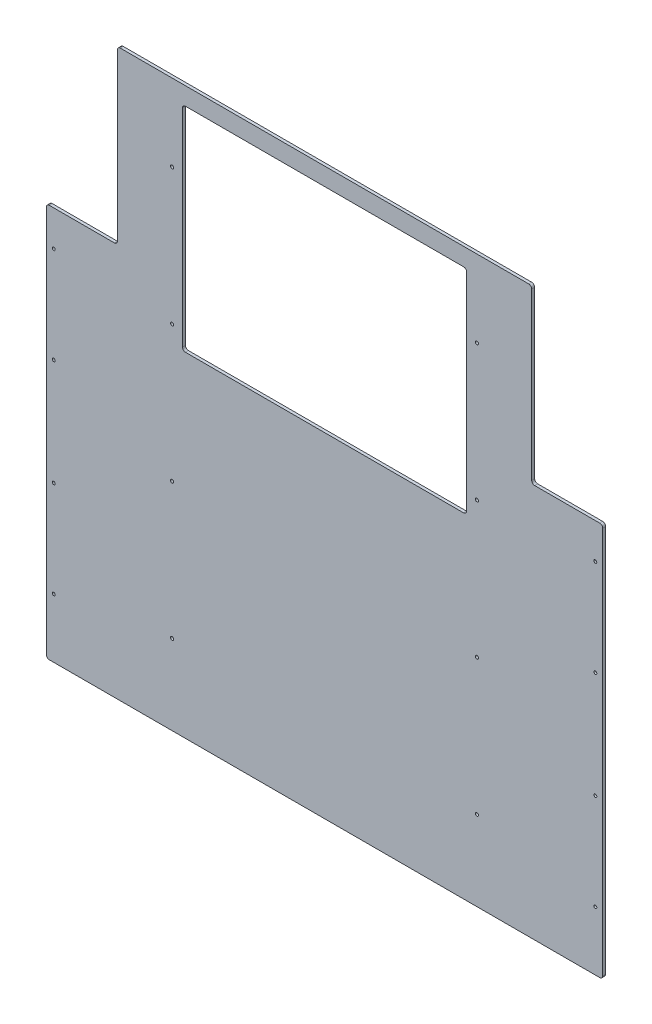
SolidWorks part; units mm, degrees
material "PC High Viscosity"
ref_plane "Front Plane" through (0, 0, 0) normal (0, 0, 1) x (1, 0, 0)
ref_plane "Top Plane" through (0, 0, 0) normal (0, 1, 0) x (1, 0, 0)
ref_plane "Right Plane" through (0, 0, 0) normal (1, 0, 0) x (0, 0, -1)
sketch "Sketch1" plane through (0, 0, 0) normal (0, 0, 1) x (1, 0, 0)
  line L1 (0, 0) -> (1193.8, 0)
  line L2 (0, 0) -> (0, 1212.85)
  line L3 (0, 1212.85) -> (1193.8, 1212.85)
  line L4 (1193.8, 0) -> (1193.8, 1212.85)
  dimension "D1" = 1212.85
  dimension "D2" = 1193.8
extrude "Boss-Extrude1" add sketch "Sketch1" along normal blind 6.35
sketch "Sketch2" plane through (0, 0, 6.35) normal (0, 0, 1) x (1, 0, 0)
  line L0 (596.9, 1212.85) -> (596.9, 0) construction
  line L1 (1193.8, 1212.85) -> (0, 1212.85) construction
  line L2 (0, 0) -> (1193.8, 0) construction
  line L3 (901.7, 1174.75) -> (292.1, 1174.75)
  line L4 (292.1, 1174.75) -> (292.1, 717.55)
  line L5 (292.1, 717.55) -> (901.7, 717.55)
  line L6 (901.7, 1174.75) -> (901.7, 717.55)
  point P11 (596.9, 717.55)
  point P12 (596.9, 1174.75)
  dimension "D1" = 609.6
  dimension "D2" = 457.2
  dimension "D3" = 38.1
extrude "Cut-Extrude1" cut sketch "Sketch2" against normal through all
sketch "Sketch3" plane through (0, 0, 6.35) normal (0, 0, 1) x (1, 0, 0)
  line L0 (0, 1212.85) -> (0, 0) construction
  line L1 (0, 1174.75) -> (152.4, 1174.75)
  line L2 (0, 1174.75) -> (0, 844.55)
  line L3 (0, 844.55) -> (152.4, 844.55)
  line L4 (152.4, 1174.75) -> (152.4, 844.55)
  line L5 (596.9, 1212.85) -> (596.9, 0) construction
  line L6 (1193.8, 1212.85) -> (0, 1212.85) construction
  line L7 (0, 0) -> (1193.8, 0) construction
  line L8 (1041.4, 1174.75) -> (1041.4, 844.55)
  line L9 (1193.8, 844.55) -> (1041.4, 844.55)
  line L10 (1193.8, 1174.75) -> (1193.8, 844.55)
  line L11 (1193.8, 1174.75) -> (1041.4, 1174.75)
  dimension "D1" = 38.1
  dimension "D2" = 368.3
  dimension "D3" = 152.4
extrude "Cut-Extrude2" cut sketch "Sketch3" against normal through all
hole_wizard "1/4 (0.25) Diameter Hole1" positions "Sketch4" profile "Sketch5" hole size "1/4" standard "ANSI Inch" end condition through all
sketch "Sketch4" plane through (0, 0, 6.35) normal (0, 0, 1) x (1, 0, 0)
  line L0 (596.9, 0) -> (596.9, 717.55) construction
  line L1 (0, 0) -> (1193.8, 0) construction
  line L2 (292.1, 717.55) -> (901.7, 717.55) construction
  line L3 (0, 844.55) -> (0, 0) construction
  point P0 (15.875, 127)
  point P2 (15.875, 333.375)
  point P4 (15.875, 561.975)
  point P6 (15.875, 768.35)
  point P17 (1177.925, 768.35)
  point P18 (1177.925, 561.975)
  point P19 (1177.925, 333.375)
  point P20 (1177.925, 127)
  dimension "D1" = 15.875
  dimension "D2" = 127
  dimension "D3" = 333.375
  dimension "D4" = 561.975
  dimension "D5" = 768.35
sketch "Sketch5" plane through (15.875, 127, 6.35) normal (1, 0, 0) x (0, -1, 0)
  line L0 (0, 0) -> (0, 6.35)
  line L1 (0, 6.35) -> (3.175, 6.35)
  line L2 (3.175, 6.35) -> (3.175, 0)
  line L5 (3.175, 0) -> (0, 0)
  line L11 (0, -6.35) -> (0, 107.95) construction
  dimension "Thru Hole Dia." = 6.35
  dimension "Thru Hole Depth" = 6.35
hole_wizard "1/4 Clearance Hole1" positions "Sketch6" profile "Sketch7" hole size "1/4" standard "ANSI Inch" end condition through all
sketch "Sketch6" plane through (0, 0, 6.35) normal (0, 0, 1) x (1, 0, 0)
  line L1 (292.1, 1212.85) -> (247.65, 1212.85)
  line L2 (292.1, 1212.85) -> (292.1, 0)
  line L3 (292.1, 0) -> (247.65, 0)
  line L4 (247.65, 1212.85) -> (247.65, 0)
  line L5 (1193.8, 1212.85) -> (0, 1212.85) construction
  line L6 (0, 0) -> (1193.8, 0) construction
  line L7 (596.9, 0) -> (596.9, 1212.85) construction
  line L8 (269.875, 1212.85) -> (269.875, 0) construction
  line L9 (923.925, 1212.85) -> (923.925, 0) construction
  line L10 (946.15, 1212.85) -> (946.15, 0)
  line L11 (901.7, 0) -> (946.15, 0)
  line L12 (901.7, 1212.85) -> (901.7, 0)
  line L13 (901.7, 1212.85) -> (946.15, 1212.85)
  line L14 (292.1, 609.6) -> (1193.8, 609.6) construction
  line L15 (1193.8, 44.45) -> (0, 44.45) construction
  line L16 (1193.8, 0) -> (1193.8, 844.55) construction
  line L17 (0, 844.55) -> (0, 0) construction
  line L19 (1193.8, 1174.75) -> (0, 1174.75) construction
  line L20 (1193.8, 1174.75) -> (1193.8, 1212.85) construction
  line L21 (0, 1212.85) -> (0, 1174.75) construction
  line L22 (1193.8, 1174.75) -> (1193.8, 44.45) construction
  point P177 (269.875, 1047.75)
  point P179 (269.875, 755.65)
  point P181 (269.875, 463.55)
  point P183 (269.875, 171.45)
  point P192 (923.925, 171.45)
  point P193 (923.925, 463.55)
  point P194 (923.925, 755.65)
  point P195 (923.925, 1047.75)
  dimension "D1" = 44.45
  dimension "D2" = 609.6
  dimension "D3" = 171.45
  dimension "D4" = 292.1
  dimension "D5" = 44.45
  dimension "D6" = 38.1
sketch "Sketch7" plane through (923.925, 1047.75, 6.35) normal (1, 0, 0) x (0, -1, 0)
  line L0 (0, 0) -> (0, 6.35)
  line L1 (0, 6.35) -> (3.3782, 6.35)
  line L2 (3.3782, 6.35) -> (3.3782, 0)
  line L5 (3.3782, 0) -> (0, 0)
  line L11 (0, -6.35) -> (0, 107.95) construction
  dimension "Thru Hole Dia." = 6.7564
  dimension "Thru Hole Depth" = 6.35
sketch "Sketch8" plane through (0, 0, 6.35) normal (0, 0, 1) x (1, 0, 0)
  line L0 (152.4, 1174.75) -> (152.4, 1212.85)
  line L1 (152.4, 1174.75) -> (0, 1174.75) construction
  line L2 (1193.8, 1212.85) -> (0, 1212.85) construction
  line L3 (152.4, 1212.85) -> (0, 1212.85)
  line L4 (0, 1212.85) -> (0, 1174.75)
  line L5 (0, 1174.75) -> (152.4, 1174.75)
  line L6 (596.9, 1212.85) -> (596.9, 0) construction
  line L7 (0, 0) -> (1193.8, 0) construction
  line L8 (1193.8, 1174.75) -> (1041.4, 1174.75)
  line L9 (1193.8, 1212.85) -> (1193.8, 1174.75)
  line L10 (1041.4, 1212.85) -> (1193.8, 1212.85)
  line L11 (1041.4, 1174.75) -> (1041.4, 1212.85)
  line L12 (152.4, 1174.75) -> (0, 1174.75) construction
  line L13 (152.4, 844.55) -> (152.4, 1174.75) construction
extrude "Cut-Extrude3" cut sketch "Sketch8" against normal through all
fillet "Fillet1" radius 6.35 12 edges at (901.7, 1174.75, 3.175) (901.7, 717.55, 3.175) (292.1, 717.55, 3.175) (152.4, 844.55, 3.175) (0, 844.55, 3.175) (0, 0, 3.175) (1193.8, 0, 3.175) (1193.8, 844.55, 3.175) (1041.4, 844.55, 3.175) (1041.4, 1212.85, 3.175) (152.4, 1212.85, 3.175) (292.1, 1174.75, 3.175)
